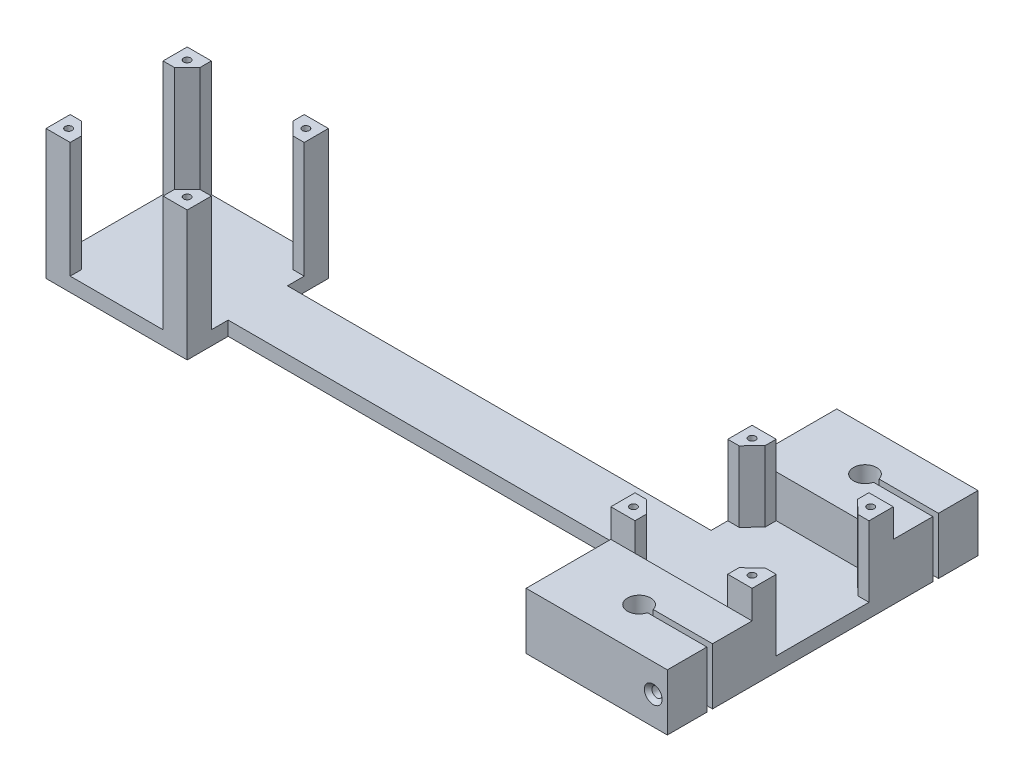
SolidWorks part; units mm, degrees
ref_plane "Front Plane" through (0, 0, 0) normal (0, 0, 1) x (1, 0, 0)
ref_plane "Top Plane" through (0, 0, 0) normal (0, 1, 0) x (1, 0, 0)
ref_plane "Right Plane" through (0, 0, 0) normal (1, 0, 0) x (0, 0, -1)
sketch "Base_sch" plane through (0, 0, 0) normal (0, 1, 0) x (1, 0, 0)
  line L5 (25, 10.5) -> (25, 25)
  line L6 (25, -25) -> (-25, -25)
  line L7 (25, 10.5) -> (175, 10.5)
  line L8 (25, -10.5) -> (175, -10.5)
  line L15 (25, -25) -> (25, -10.5)
  line L16 (25, 25) -> (-25, 25)
  line L25 (-25, -25) -> (-25, 25)
  line L28 (225.0138, -25) -> (175, -25)
  line L29 (225.0138, -25) -> (225.0138, 25)
  line L30 (225.0138, 25) -> (175, 25)
  line L31 (175, -25) -> (175, -10.5)
  line L36 (175, 10.5) -> (175, 25)
  point P0 (0, 0)
  point P1 (0, 0)
  point P8 (299.9942, 0)
  dimension "D1" = 50
  dimension "D2" = 50
  dimension "D3" = 50.0138
  dimension "D4" = 50
  dimension "D5" = 150
extrude "base_extr" add sketch "Base_sch" along normal blind 5
sketch "motor_support_sch" plane through (0, 5, 0) normal (0, 1, 0) x (1, 0, 0)
  line L0 (25, 10.5) -> (25, 25) construction
  line L5 (-25, 16.4394) -> (-25, 25)
  line L6 (-25, 25) -> (-16.4394, 25)
  line L13 (16.4394, 25) -> (25, 25)
  line L14 (25, 25) -> (25, 16.4394)
  line L15 (25, -16.4394) -> (25, -25)
  line L16 (25, -25) -> (16.4394, -25)
  line L17 (-18.7197, 18.7197) -> (-21, 16.4394)
  line L18 (-18.7197, 18.7197) -> (-16.4394, 21)
  line L19 (18.7197, 18.7197) -> (16.4394, 21)
  line L20 (18.7197, 18.7197) -> (21, 16.4394)
  line L21 (-18.7197, -18.7197) -> (-21, -16.4394)
  line L22 (-18.7197, -18.7197) -> (-16.4394, -21)
  line L23 (18.7197, -18.7197) -> (16.4394, -21)
  line L24 (18.7197, -18.7197) -> (21, -16.4394)
  line L25 (-21, 16.4394) -> (-25, 16.4394)
  line L26 (-25, 25) -> (-25, -25) construction
  line L27 (-16.4394, 21) -> (-16.4394, 25)
  line L28 (25, 25) -> (-25, 25) construction
  line L29 (16.4394, 21) -> (16.4394, 25)
  line L30 (21, 16.4394) -> (25, 16.4394)
  line L31 (-21, -16.4394) -> (-25, -16.4394)
  line L32 (-16.4394, -21) -> (-16.4394, -25)
  line L33 (-25, -25) -> (25, -25) construction
  line L34 (16.4394, -21) -> (16.4394, -25)
  line L35 (21, -16.4394) -> (25, -16.4394)
  line L36 (25, -25) -> (25, -10.5) construction
  line L37 (-25, -16.4394) -> (-25, -25)
  line L38 (-25, -25) -> (-16.4394, -25)
  point P0 (0, 0)
  point P10 (299.9942, 0)
  dimension "D7" = 41.4394
  dimension "D8" = 41.4394
extrude "Motor_1_extr" add sketch "motor_support_sch" along normal blind 41
sketch "shaft_motor_support_sch" plane through (0, 5, 0) normal (0, 1, 0) x (1, 0, 0)
  line L10 (181.2803, -18.7197) -> (179, -16.4394)
  line L11 (181.2803, -18.7197) -> (183.5606, -21)
  line L18 (179, -16.4394) -> (175, -16.4394)
  line L19 (183.5606, -21) -> (183.5606, -25)
  line L22 (175, -16.4394) -> (175, -25)
  line L23 (175, -25) -> (183.5606, -25)
  line L24 (175, 25) -> (175, 16.4025)
  line L25 (175, -24.6047) -> (175, -25)
  line L26 (175, 25) -> (175, 10.5) construction
  line L27 (175, 25) -> (183.5606, 25)
  line L28 (225.0138, -25) -> (225.0138, -16.4394)
  line L29 (225.0138, 25) -> (175, 25) construction
  line L30 (175, -10.5) -> (175, -25) construction
  line L31 (175, -25) -> (225.0138, -25) construction
  line L32 (175, 16.4025) -> (179, 16.4025)
  line L33 (183.5606, 25) -> (183.5606, 21.024)
  line L34 (183.5606, 21.024) -> (179, 16.4025)
  line L35 (225.0138, 25) -> (216.3857, 25)
  line L36 (225.0138, 25) -> (225.0138, 16.4025)
  line L37 (225.0138, -25) -> (225.0138, 25) construction
  line L38 (225.0138, 16.4025) -> (221.0566, 16.4025)
  line L39 (216.3857, 25) -> (216.3857, 21.024)
  line L40 (216.3857, 21.024) -> (221.0566, 16.4025)
  line L41 (225.0138, -25) -> (216.3857, -25)
  line L42 (216.3857, -25) -> (216.3857, -21)
  line L43 (225.0138, -16.4394) -> (221.0566, -16.4394)
  line L44 (221.0566, -16.4394) -> (216.3857, -21)
  point P0 (175, 7.9008)
  point P6 (620.659, -6.4152)
  line M11 (175, -25) -> (225.0138, -25)
  line M13 (225.0138, 25) -> (175, 25)
  dimension "D9" = 0
  dimension "D10" = 8.5606
  dimension "D11" = 4
  dimension "D12" = 3.2248
  dimension "D13" = 4
  dimension "D14" = 8.5606
  dimension "D15" = 0
extrude "shaft_motor_support_extr" add sketch "shaft_motor_support_sch" along normal blind 25 contours M13 | L18 L22 L19 L11 L10 M11 | M11 | L33 M13 region at (178.8239, 5, 21.1761) region at (221.1644, 5, 21.1848) region at (178.819, 5, -21.1622) region at (221.1693, 5, -21.1709)
hole_wizard "Tap Drill for M3x0.5 Tap1" positions "Sketch4" profile "Sketch5" hole size "M3x0.5" standard "ANSI Metric"
sketch "Sketch4" plane through (0, 46, 0) normal (0, 1, 0) x (1, 0, 0)
  point P0 (-21, -21)
  point P3 (21, -21)
  point P6 (21, 21)
  point P9 (-21, 21)
  point P12 (179.0138, 21)
  point P15 (221.0138, 21)
  point P18 (221.0138, -21)
  point P21 (179.0138, -21)
sketch "Sketch5" plane through (-21, 46, 21) normal (1, 0, 0) x (0, 0, 1)
  line L0 (0, 0) -> (0, 41.7511)
  line L1 (0, 41.7511) -> (1.25, 41)
  line L2 (1.25, 41) -> (1.25, 0)
  line L5 (1.25, 0) -> (0, 0)
  line L10 (0, 41.7511) -> (-1.25, 41) construction
  line L11 (0, -6.35) -> (0, 107.95) construction
  dimension "Hole Dia." = 2.5
  dimension "Hole Depth" = 41
  dimension "Drill Angle" = 118
sketch "Sketch12" plane through (0, 0, 0) normal (0, -1, 0) x (1, 0, 0)
  line L0 (225.0138, -25) -> (175, -25) construction
  line L1 (175, 25) -> (225.0138, 25) construction
  line L2 (175, 25) -> (175, 55)
  line L3 (225.0138, 25) -> (225.0138, 39)
  line L4 (225.0138, 55) -> (175, 55)
  line L5 (175, 25) -> (225.0138, 25)
  line L6 (175, -25) -> (175, -55)
  line L7 (225.0138, -25) -> (225.0138, -39)
  line L8 (225.0138, -55) -> (175, -55)
  line L9 (175, -25) -> (225.0138, -25)
  line L10 (203.9831, -39) -> (225.0138, -39)
  line L11 (225.0138, -41) -> (203.9831, -41)
  line L12 (225.0138, 41) -> (203.9831, 41)
  line L13 (225.0138, 39) -> (203.9831, 39)
  line L14 (225.0138, 41) -> (225.0138, 55)
  line L15 (225.0138, -41) -> (225.0138, -55)
  arc A0 (203.9831, 41) -> (203.9831, 39) centre (200.0069, 40) ccw
  arc A1 (203.9831, -39) -> (203.9831, -41) centre (200.0069, -40) ccw
  dimension "D1" = 8.2
  dimension "D2" = 8.2
  dimension "D3" = 15
  dimension "D4" = 15
  dimension "D5" = 30
  dimension "D6" = 30
  dimension "D7" = 1
  dimension "D8" = 1
  dimension "D9" = 1
  dimension "D10" = 1
extrude "Boss-Extrude10" add sketch "Sketch12" against normal blind 20
hole_wizard "CSK for M3 Oval Head Machine Screw1" positions "3DSketch1" profile "Sketch14" countersink size "M3" standard "ANSI Metric"
sketch3d "3DSketch1"
  line L0 (225.0138, 20, 55) -> (175, 20, 55) construction
  line L1 (225.0138, 20, 55) -> (225.0138, 0, 55) construction
  point P0 (220.0138, 10, 55)
  dimension "D1" = 10
  dimension "D2" = 5
sketch "Sketch14" plane through (220.0138, 10, 55) normal (1, 0, 0) x (0, -1, 0)
  line L0 (0, 0) -> (0, 15.0815)
  line L1 (0, 15.0815) -> (1.8, 14)
  line L2 (1.8, 14) -> (1.8, 1.35)
  line L3 (1.8, 1.35) -> (3.15, 0)
  line L5 (3.15, 0) -> (0, 0)
  line L6 (-1.8, 1.35) -> (-3.15, 0) construction
  line L10 (0, 15.0815) -> (-1.8, 14) construction
  line L11 (0, -6.35) -> (0, 107.95) construction
  dimension "Hole Dia." = 3.6
  dimension "Hole Depth" = 14
  dimension "Near C'Sink Dia." = 6.3
  dimension "Near C'Sink Angle" = 90
  dimension "Drill Angle" = 118
hole_wizard "CSK for M3 Oval Head Machine Screw2" positions "3DSketch2" profile "Sketch15" countersink size "M3" standard "ANSI Metric"
sketch3d "3DSketch2"
  line L0 (175, 20, -55) -> (225.0138, 20, -55) construction
  line L1 (225.0138, 20, -55) -> (225.0138, 0, -55) construction
  point P0 (220.0138, 10, -55)
  dimension "D1" = 10
  dimension "D2" = 5
sketch "Sketch15" plane through (220.0138, 10, -55) normal (1, 0, 0) x (0, 1, 0)
  line L0 (0, 0) -> (0, 15.0815)
  line L1 (0, 15.0815) -> (1.8, 14)
  line L2 (1.8, 14) -> (1.8, 1.35)
  line L3 (1.8, 1.35) -> (3.15, 0)
  line L5 (3.15, 0) -> (0, 0)
  line L6 (-1.8, 1.35) -> (-3.15, 0) construction
  line L10 (0, 15.0815) -> (-1.8, 14) construction
  line L11 (0, -6.35) -> (0, 107.95) construction
  dimension "Hole Dia." = 3.6
  dimension "Hole Depth" = 14
  dimension "Near C'Sink Dia." = 6.3
  dimension "Near C'Sink Angle" = 90
  dimension "Drill Angle" = 118
